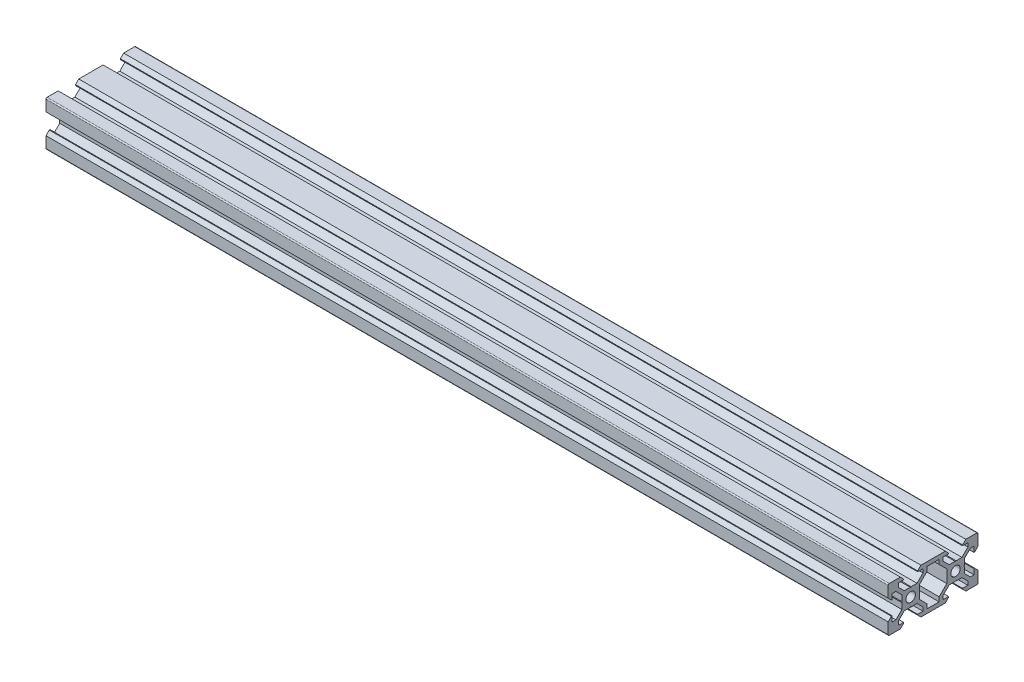
SolidWorks part; units mm, degrees
material "6061-T6 (SS)"
ref_plane "Top" through (0, 0, 0) normal (0, 0, 1) x (1, 0, 0)
ref_plane "Front" through (0, 0, 0) normal (0, 1, 0) x (1, 0, 0)
ref_plane "Right" through (0, 0, 0) normal (1, 0, 0) x (0, 0, -1)
sketch "Profile Sketch" plane through (0, 0, 0) normal (1, 0, 0) x (0, 0, -1)
  line L0 (5.42, 10) -> (-5.42, 10)
  line L1 (-4.5, 8.2) -> (-4.5, 6.56)
  line L2 (-4.5, 6.56) -> (-7.16, 3.9)
  line L3 (-7.16, 3.9) -> (-9.79, 3.9)
  line L4 (-9.79, 3.9) -> (-10, 3.69)
  line L5 (2.7, 8.2) -> (-2.7, 8.2)
  line L6 (-2.7, 8.2) -> (-2.7, 6.2387)
  line L7 (-2.7, 6.2387) -> (-6.1, 2.8387)
  line L8 (-6.1, 2.8387) -> (-6.1, -0.21)
  line L9 (-6.875, 8.545) -> (-6.875, 8.2)
  line L10 (-6.875, 8.2) -> (-4.5, 8.2)
  line L11 (-6.875, 8.545) -> (-5.42, 10)
  line L12 (0, -10) -> (0, 10) construction
  line L13 (-20, 0) -> (20, 0) construction
  line L14 (-10, -10) -> (-10, 10) construction
  line L15 (-6.875, -8.545) -> (-5.42, -10)
  line L16 (-6.875, -8.2) -> (-4.5, -8.2)
  line L17 (-6.875, -8.545) -> (-6.875, -8.2)
  line L18 (-2.7, -6.2387) -> (-6.1, -2.8387)
  line L19 (-2.7, -8.2) -> (-2.7, -6.2387)
  line L20 (2.7, -8.2) -> (-2.7, -8.2)
  line L21 (-7.16, -3.9) -> (-9.79, -3.9)
  line L22 (-4.5, -6.56) -> (-7.16, -3.9)
  line L23 (-4.5, -8.2) -> (-4.5, -6.56)
  line L24 (5.42, -10) -> (-5.42, -10)
  line L25 (-10, 0) -> (-20, 10) construction
  line L26 (-18.545, 3.125) -> (-18.2, 3.125)
  line L27 (-13.125, -8.545) -> (-13.125, -8.2)
  line L28 (-13.125, -8.2) -> (-15.5, -8.2)
  line L29 (-13.125, -8.545) -> (-14.58, -10)
  line L30 (-15.5, -8.2) -> (-15.5, -6.56)
  line L31 (-15.5, -6.56) -> (-12.84, -3.9)
  line L32 (-12.84, -3.9) -> (-10.21, -3.9)
  line L33 (-20, 4.58) -> (-20, 9.5)
  line L34 (-13.9, 2.8387) -> (-13.9, 0.21)
  line L35 (-16.56, 5.5) -> (-13.9, 2.8387)
  line L36 (-12.84, 3.9) -> (-10.21, 3.9)
  line L37 (-15.5, 6.56) -> (-12.84, 3.9)
  line L38 (-15.5, 8.2) -> (-15.5, 6.56)
  line L39 (-13.125, 8.545) -> (-14.58, 10)
  line L40 (-13.125, 8.2) -> (-15.5, 8.2)
  line L41 (-13.125, 8.545) -> (-13.125, 8.2)
  line L42 (-18.2, 3.125) -> (-18.2, 5.5)
  line L43 (-18.545, 3.125) -> (-20, 4.58)
  line L44 (-18.2, 5.5) -> (-16.56, 5.5)
  line L45 (-14.58, 10) -> (-19.5, 10)
  line L46 (-16.56, -5.5) -> (-13.9, -2.8387)
  line L47 (-14.58, -10) -> (-19.5, -10)
  line L48 (-18.2, -5.5) -> (-16.56, -5.5)
  line L49 (-18.545, -3.125) -> (-20, -4.58)
  line L50 (-18.2, -3.125) -> (-18.2, -5.5)
  line L51 (-20, -4.58) -> (-20, -9.5)
  line L52 (-18.545, -3.125) -> (-18.2, -3.125)
  line L53 (10, -10) -> (10, 10) construction
  line L54 (18.545, -3.125) -> (18.2, -3.125)
  line L55 (20, -4.58) -> (20, -9.5)
  line L56 (18.2, -3.125) -> (18.2, -5.5)
  line L57 (18.545, -3.125) -> (20, -4.58)
  line L58 (18.2, -5.5) -> (16.56, -5.5)
  line L59 (14.58, -10) -> (19.5, -10)
  line L60 (16.56, -5.5) -> (13.9, -2.8387)
  line L61 (14.58, 10) -> (19.5, 10)
  line L62 (18.2, 5.5) -> (16.56, 5.5)
  line L63 (18.545, 3.125) -> (20, 4.58)
  line L64 (18.2, 3.125) -> (18.2, 5.5)
  line L65 (13.125, 8.545) -> (13.125, 8.2)
  line L66 (13.125, 8.2) -> (15.5, 8.2)
  line L67 (13.125, 8.545) -> (14.58, 10)
  line L68 (15.5, 8.2) -> (15.5, 6.56)
  line L69 (15.5, 6.56) -> (12.84, 3.9)
  line L70 (12.84, 3.9) -> (10.21, 3.9)
  line L71 (16.56, 5.5) -> (13.9, 2.8387)
  line L72 (13.9, 2.8387) -> (13.9, 0.21)
  line L73 (20, 4.58) -> (20, 9.5)
  line L74 (12.84, -3.9) -> (10.21, -3.9)
  line L75 (15.5, -6.56) -> (12.84, -3.9)
  line L76 (15.5, -8.2) -> (15.5, -6.56)
  line L77 (13.125, -8.545) -> (14.58, -10)
  line L78 (13.125, -8.2) -> (15.5, -8.2)
  line L79 (13.125, -8.545) -> (13.125, -8.2)
  line L80 (18.545, 3.125) -> (18.2, 3.125)
  line L81 (4.5, -8.2) -> (4.5, -6.56)
  line L82 (4.5, -6.56) -> (7.16, -3.9)
  line L83 (7.16, -3.9) -> (9.79, -3.9)
  line L84 (2.7, -8.2) -> (2.7, -6.2387)
  line L85 (2.7, -6.2387) -> (6.1, -2.8387)
  line L86 (6.875, -8.545) -> (6.875, -8.2)
  line L87 (6.875, -8.2) -> (4.5, -8.2)
  line L88 (6.875, -8.545) -> (5.42, -10)
  line L89 (6.875, 8.545) -> (5.42, 10)
  line L90 (6.875, 8.2) -> (4.5, 8.2)
  line L91 (6.875, 8.545) -> (6.875, 8.2)
  line L92 (6.1, 2.8387) -> (6.1, -0.21)
  line L93 (2.7, 6.2387) -> (6.1, 2.8387)
  line L94 (2.7, 8.2) -> (2.7, 6.2387)
  line L95 (9.79, 3.9) -> (10, 3.69)
  line L96 (7.16, 3.9) -> (9.79, 3.9)
  line L97 (4.5, 6.56) -> (7.16, 3.9)
  line L98 (4.5, 8.2) -> (4.5, 6.56)
  line L99 (-10, 3.69) -> (-10.21, 3.9)
  line L100 (-10, -3.69) -> (-10.21, -3.9)
  line L101 (-9.79, -3.9) -> (-10, -3.69)
  line L102 (-13.9, -0.21) -> (-13.69, 0)
  line L103 (-13.69, 0) -> (-13.9, 0.21)
  line L104 (-13.9, -0.21) -> (-13.9, -2.8387)
  line L105 (-6.1, -0.21) -> (-6.31, 0)
  line L106 (-6.31, 0) -> (-6.1, -0.21)
  line L107 (-6.1, -0.21) -> (-6.1, -2.8387)
  line L108 (6.31, 0) -> (6.1, -0.21)
  line L109 (6.1, -0.21) -> (6.31, 0)
  line L110 (13.69, 0) -> (13.9, 0.21)
  line L111 (13.9, -0.21) -> (13.69, 0)
  line L112 (9.79, -3.9) -> (10, -3.69)
  line L113 (10, -3.69) -> (10.21, -3.9)
  line L114 (10, 3.69) -> (10.21, 3.9)
  line L115 (6.1, -0.21) -> (6.1, -2.8387)
  line L116 (13.9, -0.21) -> (13.9, -2.8387)
  line L118 (20, -10) -> (20, 10) construction
  line L119 (20, -10) -> (-20, -10) construction
  line L120 (-20, -10) -> (-20, 10) construction
  line L121 (20, 10) -> (-20, 10) construction
  line L122 (20, -10) -> (-20, 10) construction
  line L123 (-20, -10) -> (20, 10) construction
  circle A0 centre (-10, 0) radius 2.1
  arc A1 (-19.5, 10) -> (-20, 9.5) centre (-19.5, 9.5) ccw
  arc A2 (-19.5, -10) -> (-20, -9.5) centre (-19.5, -9.5) cw
  arc A3 (19.5, -10) -> (20, -9.5) centre (19.5, -9.5) ccw
  arc A4 (19.5, 10) -> (20, 9.5) centre (19.5, 9.5) cw
  circle A5 centre (10, 0) radius 2.1
  point P35 (-2.4957, 0)
  point P108 (0, -8.2)
  point P119 (0, 8.2)
  point P123 (2.4957, 0)
  point P131 (0, 0)
  point P143 (0, 0)
  dimension "D4" = 5.42
  dimension "D5" = 40
  dimension "D6" = 4.2
  dimension "D16" = 0.5
  dimension "D1" = 0.21
  dimension "D2" = 45
  dimension "D3" = 20
  dimension "D7" = 1.5
  dimension "D8" = 1.8
  dimension "D9" = 10
  dimension "D10" = 3.9
  dimension "D11" = 3.9
  dimension "D12" = 1.8
  dimension "D13" = 3.125
  dimension "D14" = 5.5
  dimension "D15" = 1.64
  dimension "D17" = 5.4
extrude "Profile Extrude" add sketch "Profile Sketch" along normal blind 375 contours A4 L61 L67 L65 L66 L68 L69 L70 L114 L95 L96 L97 L98 L90 L91 L89 L0 L11 L9 L10 L1 L2 L3 L4 L99 L36 L37 L38 L40 L41 L39 L45 A1 L33 L43 L26 L42 L44 L35 L34 L103 L102 L104 L46 L48 L50 L52 L49 L51 A2 L47 region at (0, 8.9563, -5.8313)
equation "\"M2x0.4_Tap_Hole_75\"= 1.6"
